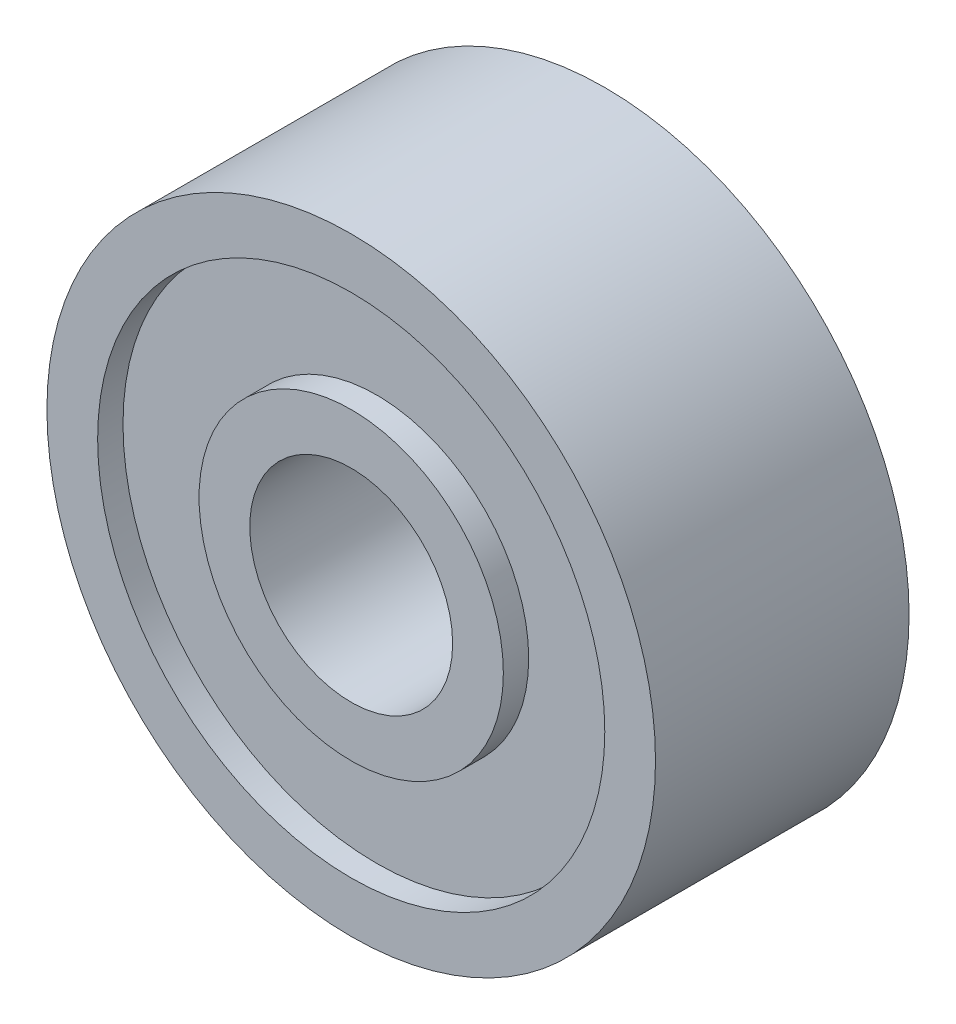
SolidWorks part; units mm, degrees
ref_plane "Alzado" through (0, 0, 0) normal (0, 0, 1) x (1, 0, 0)
ref_plane "Planta" through (0, 0, 0) normal (0, 1, 0) x (1, 0, 0)
ref_plane "Vista lateral" through (0, 0, 0) normal (1, 0, 0) x (0, 0, -1)
sketch "Croquis1" plane through (0, 0, 0) normal (0, 0, 1) x (1, 0, 0)
  circle A0 centre (0, 0) radius 6
  circle A1 centre (0, 0) radius 2
  circle A2 centre (0, 0) radius 5
  circle A3 centre (0, 0) radius 3
  dimension "D1" = 12
  dimension "D2" = 4
  dimension "D3" = 1
  dimension "D4" = 1
extrude "Saliente-Extruir2" add sketch "Croquis1" along normal blind 2.5 and the other way blind 2.5 contours A0 A2 | A3 A1 region at (-5.8303, 0, 0) region at (-2.9151, 0, 0)
extrude "Saliente-Extruir3" add sketch "Croquis1<3>" along normal blind 2 and the other way blind 2 contours A2 A3 region at (-4.8586, 0, 0)
sketch "Croquis1<3>" plane through (0, 0, 0) normal (0, 0, 1) x (1, 0, 0) same geometry as "Croquis1"
